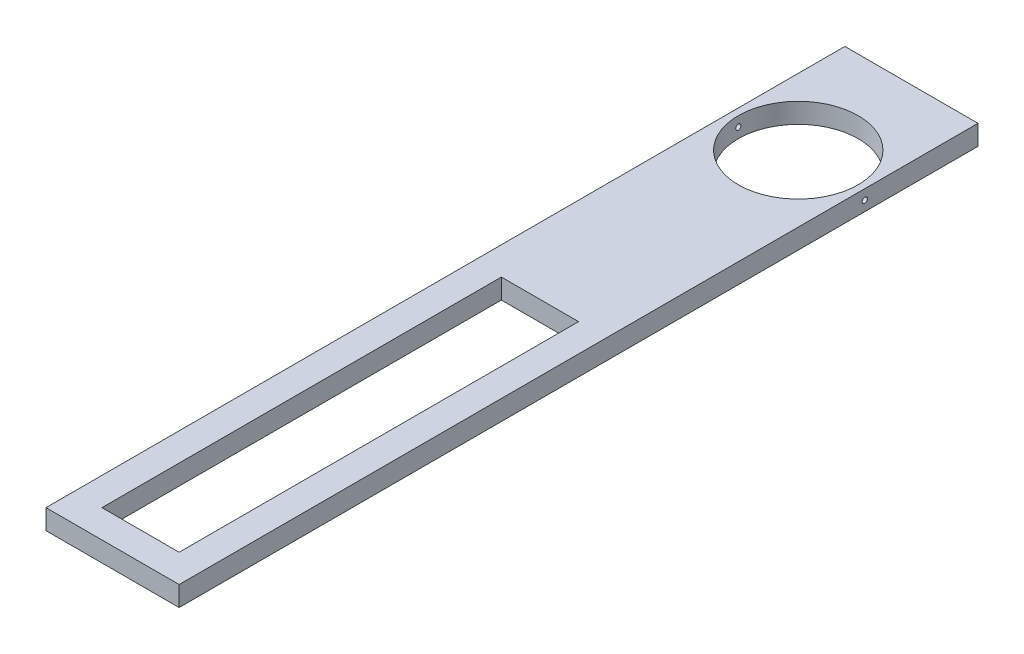
SolidWorks part; units mm, degrees
note: The reader was unsure of these and kept them because the rebuilt part matched: shared geometry of "Sketch1<7>", "Sketch1<8>".
material "ABS"
ref_plane "Ön Düzlem" through (0, 0, 0) normal (0, 0, 1) x (1, 0, 0)
ref_plane "Üst Düzlem" through (0, 0, 0) normal (0, 1, 0) x (1, 0, 0)
ref_plane "Sağ Düzlem" through (0, 0, 0) normal (1, 0, 0) x (0, 0, -1)
sketch "Sketch1" plane through (0, 0, 0) normal (0, 1, 0) x (1, 0, 0)
  line L1 (-50, 429) -> (50, 429)
  line L2 (-50, 429) -> (-50, -171)
  line L3 (-50, -171) -> (50, -171)
  line L4 (50, 429) -> (50, -171)
  line L5 (-29, 150) -> (29, 150)
  line L6 (-29, 150) -> (-29, -150)
  line L7 (-29, -150) -> (29, -150)
  line L8 (29, 150) -> (29, -150)
  line L24 (-50, 0) -> (-29, 0) construction
  line L25 (0, -150) -> (0, -171) construction
  circle A9 centre (0, 344) radius 45
  point P14 (-29, 0)
  point P22 (0, -171)
  point P32 (0, -150)
  dimension "D2" = 58
  dimension "D4" = 90
  dimension "D7" = 85
  dimension "D1" = 600
  dimension "D5" = 300
  dimension "D6" = 100
extrude "Boss-Extrude2" add sketch "Sketch1" against normal blind 15
extrude "Cut-Extrude1" cut sketch "Sketch1<7>" against normal blind 65
sketch "Sketch1<7>" plane through (0, 0, 0) normal (0, 1, 0) x (1, 0, 0) same geometry as "Sketch1"
extrude "Cut-Extrude2" cut sketch "Sketch1<8>" against normal through all contours A9
sketch "Sketch1<8>" plane through (0, 0, 0) normal (0, 1, 0) x (1, 0, 0) same geometry as "Sketch1"
ref_plane "Plane1" through (47.5, 0, 0) normal (1, 0, 0) x (0, 0, -1)
sketch "Sketch5" plane through (47.5, 0, 0) normal (1, 0, 0) x (0, 0, -1)
  line L0 (299, -15) -> (389, -15) construction
  line L1 (389, 0) -> (299, 0) construction
  line L2 (299, -15) -> (389, -15)
  line L3 (389, 0) -> (299, 0)
  line L4 (344, 0) -> (344, -15) construction
  circle A0 centre (344, -7.5) radius 2
  dimension "D1" = 4
extrude "Cut-Extrude4" cut sketch "Sketch5" against normal through all both and the other way through all contours A0 L4 | L4 A0
